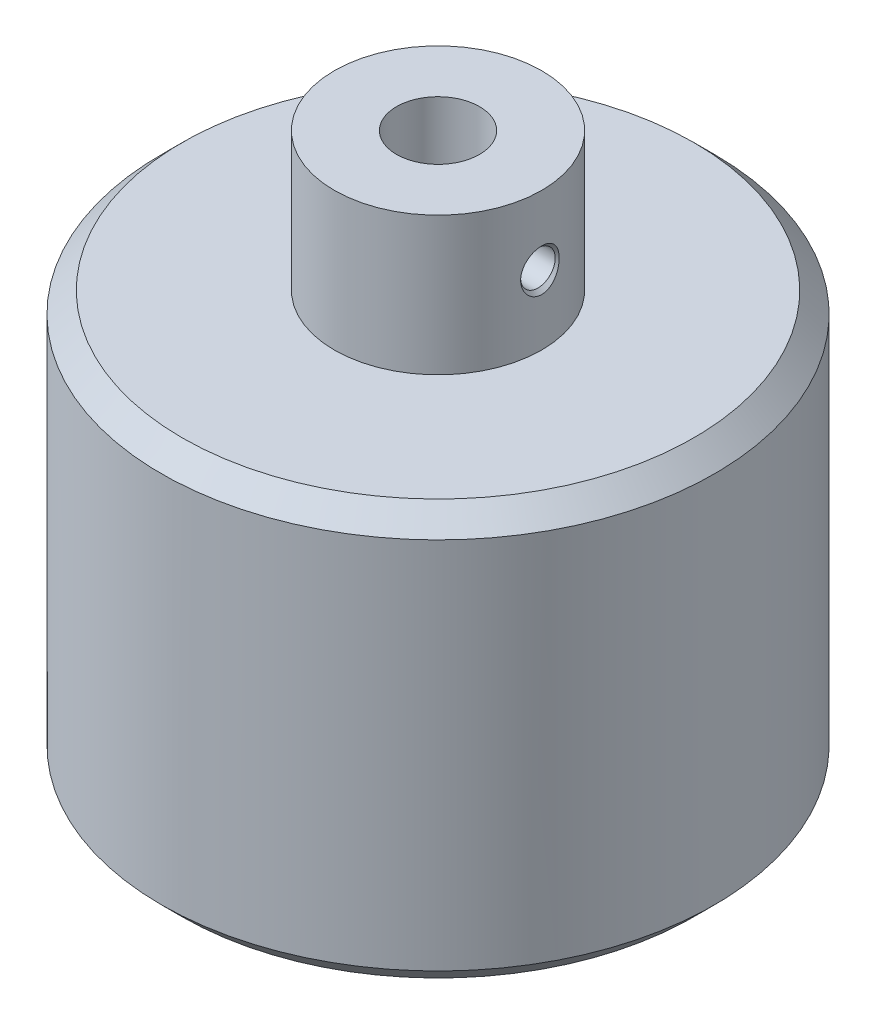
SolidWorks part; units mm, degrees
material "AISI 304"
ref_plane "Front Plane" through (0, 0, 0) normal (0, 0, 1) x (1, 0, 0)
ref_plane "Top Plane" through (0, 0, 0) normal (0, 1, 0) x (1, 0, 0)
ref_plane "Right Plane" through (0, 0, 0) normal (1, 0, 0) x (0, 0, -1)
sketch "Sketch2" plane through (0, 0, 0) normal (0, 1, 0) x (1, 0, 0)
  circle A0 centre (0, 0) radius 20
  dimension "D1" = 40
extrude "Boss-Extrude1" add sketch "Sketch2" along normal blind 30 contours A0
sketch "Sketch6" plane through (0, 0, 0) normal (0, 1, 0) x (1, 0, 0)
  circle A0 centre (0, 0) radius 7.5
  dimension "D1" = 15
extrude "Boss-Extrude3" add sketch "Sketch6" along normal blind 40
sketch "Sketch7" plane through (0, 40, 0) normal (0, 1, 0) x (1, 0, 0)
  circle A0 centre (0, 0) radius 3
  dimension "D1" = 6
extrude "Cut-Extrude1" cut sketch "Sketch7" against normal through all
hole_wizard "M3 Tapped Hole1" positions "3DSketch1" profile "Sketch8" tap size "M3" standard "ISO" end condition up to next
sketch3d "3DSketch1"
  point P0 (7.5, 35, 0)
  dimension "D1" = 35
sketch "Sketch8" plane through (7.5, 35, 0) normal (0, 1, 0) x (0, 0, -1)
  line L0 (0, 0) -> (0, 4.5)
  line L1 (0, 4.5) -> (1.25, 4.5)
  line L2 (1.25, 4.5) -> (1.25, 0.275)
  line L3 (1.25, 0.275) -> (1.525, 0)
  line L5 (1.525, 0) -> (0, 0)
  line L6 (-1.25, 0.275) -> (-1.525, 0) construction
  line L11 (0, -6.35) -> (0, 107.95) construction
  dimension "Thru Tap Drill Dia." = 2.5
  dimension "Thru Tap Drill Depth" = 4.5
  dimension "Near C'Sink Dia." = 3.05
  dimension "Near C'Sink Angle" = 90
cosmetic thread "Hole Thread1" parameters "D2"=3
chamfer "Chamfer1" distance 1.5 angle 45 2 edges at (0, 0, 20) (0, 30, 20)
